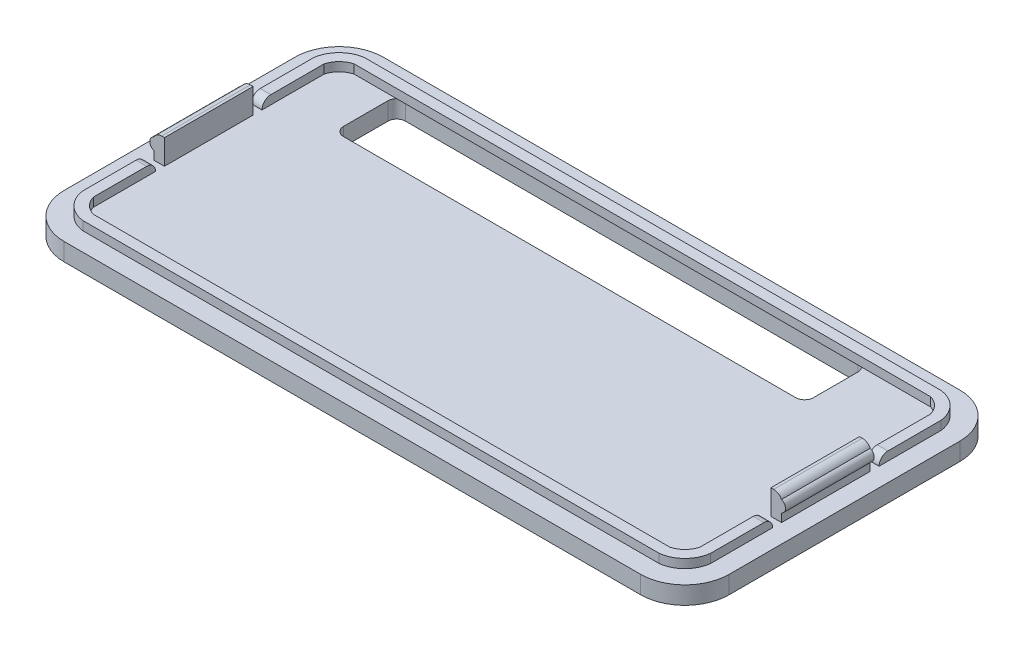
SolidWorks part; units mm, degrees
ref_plane "前视基准面" through (0, 0, 0) normal (0, 0, 1) x (1, 0, 0)
ref_plane "上视基准面" through (0, 0, 0) normal (0, 1, 0) x (1, 0, 0)
ref_plane "右视基准面" through (0, 0, 0) normal (1, 0, 0) x (0, 0, -1)
sketch "zero" plane through (0, 0, 0) normal (0, 1, 0) x (1, 0, 0)
  line L1 (-29.5, 15) -> (29.5, 15)
  line L2 (-32.5, 12) -> (-32.5, -12)
  line L3 (-29.5, -15) -> (29.5, -15)
  line L4 (32.5, 12) -> (32.5, -12)
  line L5 (-32.5, 15) -> (32.5, -15) construction
  line L6 (-32.5, -15) -> (32.5, 15) construction
  line L7 (-25.7, -15) -> (-14.5, -15)
  line L8 (-25.7, -15) -> (-25.7, -9.6569)
  line L9 (-25.7, -9.6569) -> (-14.5, -9.6569)
  line L10 (-14.5, -15) -> (-14.5, -9.6569)
  line L11 (5.2, -15) -> (12.7, -15)
  line L12 (5.2, -15) -> (5.2, -11)
  line L13 (5.2, -11) -> (12.7, -11)
  line L14 (12.7, -15) -> (12.7, -11)
  line L15 (17.8, -15) -> (25.3, -15)
  line L16 (17.8, -15) -> (17.8, -11)
  line L17 (17.8, -11) -> (25.3, -11)
  line L18 (25.3, -15) -> (25.3, -11)
  line L19 (-32.5, 7.7) -> (-19.5, 7.7)
  line L20 (-32.5, 7.7) -> (-32.5, -4.3)
  line L21 (-32.5, -4.3) -> (-19.5, -4.3)
  line L22 (-19.5, 7.7) -> (-19.5, -4.3)
  line L23 (-25.5, 14) -> (25.5, 14)
  line L24 (-25.5, 14) -> (-25.5, 8.8)
  line L25 (-25.5, 8.8) -> (25.5, 8.8)
  line L26 (25.5, 14) -> (25.5, 8.8)
  line L27 (-19.5, 7.2329) -> (-35.5, 7.2329)
  line L28 (-19.5, 7.2329) -> (-19.5, -3.7671)
  line L29 (-19.5, -3.7671) -> (-35.5, -3.7671)
  line L30 (-35.5, 7.2329) -> (-35.5, -3.7671)
  arc A0 (29.5, -15) -> (32.5, -12) centre (29.5, -12) ccw
  arc A1 (29.5, 15) -> (32.5, 12) centre (29.5, 12) cw
  arc A2 (-32.5, -12) -> (-29.5, -15) centre (-29.5, -12) ccw
  arc A3 (-29.5, 15) -> (-32.5, 12) centre (-29.5, 12) ccw
  circle A4 centre (-29, 11.4) radius 3
  circle A5 centre (-29, -11.5) radius 3
  circle A6 centre (29, 11.4) radius 3
  circle A7 centre (29, -11.5) radius 3
  circle A8 centre (-29, 11.4) radius 1.375
  circle A9 centre (-29, -11.5) radius 1.375
  circle A10 centre (29, -11.5) radius 1.375
  circle A11 centre (29, 11.4) radius 1.375
  point P0 (0, 0)
  dimension "D3" = 3
  dimension "D4" = 6
  dimension "D9" = 2.75
  dimension "D1" = 65
  dimension "D2" = 30
  dimension "D5" = 3.6
  dimension "D6" = 3.5
  dimension "D7" = 3.5
  dimension "D8" = 3.5
  dimension "D10" = 12
  dimension "D11" = 7.3
  dimension "D12" = 13
  dimension "D13" = 11.2
  dimension "D14" = 6.8
  dimension "D15" = 19.7
  dimension "D16" = 7.5
  dimension "D17" = 7.5
  dimension "D18" = 5.1
  dimension "D19" = 4
  dimension "D20" = 5.2
  dimension "D21" = 7
  dimension "D22" = 7
  dimension "D23" = 1
  dimension "D24" = 11
  dimension "D25" = 16
sketch "sugar" plane through (0, 0, 0) normal (0, 1, 0) x (1, 0, 0)
  line L1 (-29.5, 15) -> (29.5, 15)
  line L2 (-32.5, 12) -> (-32.5, -12)
  line L3 (-29.5, -15) -> (29.5, -15)
  line L4 (32.5, 12) -> (32.5, -12)
  line L5 (-32.5, 15) -> (32.5, -15) construction
  line L6 (-32.5, -15) -> (32.5, 15) construction
  line L7 (23.5, -11.5) -> (19.5, -11.5)
  line L8 (23.5, -11.5) -> (23.5, -13.9082)
  line L9 (23.5, -13.9082) -> (19.5, -13.9082)
  line L10 (19.5, -11.5) -> (19.5, -13.9082)
  line L11 (16, -11.0071) -> (8.5, -11.0071)
  line L12 (16, -11.0071) -> (16, -15)
  line L13 (16, -15) -> (8.5, -15)
  line L14 (8.5, -11.0071) -> (8.5, -15)
  line L15 (20.5, -13.9082) -> (22.5, -13.9082)
  line L16 (20.5, -13.9082) -> (20.5, -14.8173)
  line L17 (20.5, -14.8173) -> (22.5, -14.8173)
  line L18 (22.5, -13.9082) -> (22.5, -14.8173)
  arc A0 (29.5, 15) -> (32.5, 12) centre (29.5, 12) cw
  arc A1 (29.5, -15) -> (32.5, -12) centre (29.5, -12) ccw
  arc A2 (-32.5, -12) -> (-29.5, -15) centre (-29.5, -12) ccw
  arc A3 (-29.5, 15) -> (-32.5, 12) centre (-29.5, 12) ccw
  circle A4 centre (-29, 11.4) radius 3
  circle A5 centre (-29, 11.4) radius 1.375
  circle A6 centre (-29, -11.5) radius 3
  circle A7 centre (-29, -11.5) radius 1.375
  circle A8 centre (29, 11.4) radius 3
  circle A9 centre (29, 11.4) radius 1.375
  circle A10 centre (29, -11.5) radius 3
  circle A11 centre (29, -11.5) radius 1.375
  dimension "D3" = 3
  dimension "D1" = 65
  dimension "D2" = 30
  dimension "D4" = 9
  dimension "D5" = 4
  dimension "D6" = 3.5
  dimension "D7" = 7.5
  dimension "D8" = 2
  dimension "D9" = 1
sketch "case" plane through (0, 0, 0) normal (0, 1, 0) x (1, 0, 0)
  line L1 (-34.0422, 18) -> (30.9578, 18)
  line L2 (-39.0422, 13) -> (-39.0422, -13)
  line L3 (-34.0422, -18) -> (30.9578, -18)
  line L4 (35.9578, 13) -> (35.9578, -13)
  line L5 (-39.0422, 18) -> (35.9578, -18) construction
  line L6 (-39.0422, -18) -> (35.9578, 18) construction
  arc A0 (-39.0422, -13) -> (-34.0422, -18) centre (-34.0422, -13) ccw
  arc A1 (30.9578, -18) -> (35.9578, -13) centre (30.9578, -13) ccw
  arc A2 (30.9578, 18) -> (35.9578, 13) centre (30.9578, 13) cw
  arc A3 (-34.0422, 18) -> (-39.0422, 13) centre (-34.0422, 13) ccw
  point P0 (-1.5422, 0)
  point P3 (-1.5422, 0)
  dimension "D3" = 5
  dimension "D1" = 75
  dimension "D2" = 36
extrude "凸台-拉伸2" add sketch "case" along normal blind 2
sketch "草图2" plane through (0, 0, 0) normal (0, 1, 0) x (1, 0, 0)
  line L4 (-34.0422, -14.7) -> (30.9578, -14.7)
  line L5 (32.6578, -13) -> (32.6578, 13)
  line L6 (30.9578, 14.7) -> (-34.0422, 14.7)
  line L7 (-35.7422, 13) -> (-35.7422, -13)
  line L12 (33.8578, -13) -> (33.8578, 13)
  line L13 (30.9578, 15.9) -> (-34.0422, 15.9)
  line L14 (-36.9422, 13) -> (-36.9422, -13)
  line L15 (-34.0422, -15.9) -> (30.9578, -15.9)
  arc A4 (30.9578, -14.7) -> (32.6578, -13) centre (30.339, -12.3812) ccw
  arc A5 (32.6578, 13) -> (30.9578, 14.7) centre (30.339, 12.3812) ccw
  arc A6 (-34.0422, 14.7) -> (-35.7422, 13) centre (-33.4234, 12.3812) ccw
  arc A7 (-35.7422, -13) -> (-34.0422, -14.7) centre (-33.4234, -12.3812) ccw
  arc A12 (30.9578, -15.9) -> (33.8578, -13) centre (30.5796, -12.6217) ccw
  arc A13 (33.8578, 13) -> (30.9578, 15.9) centre (30.5796, 12.6217) ccw
  arc A14 (-34.0422, 15.9) -> (-36.9422, 13) centre (-33.6639, 12.6217) ccw
  arc A15 (-36.9422, -13) -> (-34.0422, -15.9) centre (-33.6639, -12.6217) ccw
  point P13 (0, 0)
  point P14 (0, 0)
ref_plane "基准面1" through (0, 2, 0) normal (0, 1, 0) x (1, 0, 0)
sketch "草图3" plane through (0, 2, 0) normal (0, 1, 0) x (1, 0, 0)
  line L4 (-34.0422, -14.7) -> (30.9578, -14.7)
  line L5 (32.6578, -13) -> (32.6578, 13)
  line L6 (30.9578, 14.7) -> (-34.0422, 14.7)
  line L7 (-35.7422, 13) -> (-35.7422, -13)
  line L8 (-34.0422, -14.7) -> (30.9578, -14.7)
  line L9 (32.6578, -13) -> (32.6578, 13)
  line L10 (30.9578, 14.7) -> (-34.0422, 14.7)
  line L11 (-35.7422, 13) -> (-35.7422, -13)
  line L12 (-36.9422, 13) -> (-36.9422, -13)
  line L13 (-34.0422, -15.9) -> (30.9578, -15.9)
  line L14 (33.8578, -13) -> (33.8578, 13)
  line L15 (30.9578, 15.9) -> (-34.0422, 15.9)
  line L16 (-36.9422, 13) -> (-36.9422, -13)
  line L17 (-34.0422, -15.9) -> (30.9578, -15.9)
  line L18 (33.8578, -13) -> (33.8578, 13)
  line L19 (30.9578, 15.9) -> (-34.0422, 15.9)
  arc A4 (30.9578, -14.7) -> (32.6578, -13) centre (30.339, -12.3812) ccw
  arc A5 (32.6578, 13) -> (30.9578, 14.7) centre (30.339, 12.3812) ccw
  arc A6 (-34.0422, 14.7) -> (-35.7422, 13) centre (-33.4234, 12.3812) ccw
  arc A7 (-35.7422, -13) -> (-34.0422, -14.7) centre (-33.4234, -12.3812) ccw
  arc A8 (30.9578, -14.7) -> (32.6578, -13) centre (30.339, -12.3812) ccw
  arc A9 (32.6578, 13) -> (30.9578, 14.7) centre (30.339, 12.3812) ccw
  arc A10 (-34.0422, 14.7) -> (-35.7422, 13) centre (-33.4234, 12.3812) ccw
  arc A11 (-35.7422, -13) -> (-34.0422, -14.7) centre (-33.4234, -12.3812) ccw
  arc A12 (-36.9422, -13) -> (-34.0422, -15.9) centre (-33.6639, -12.6217) ccw
  arc A13 (30.9578, -15.9) -> (33.8578, -13) centre (30.5796, -12.6217) ccw
  arc A14 (33.8578, 13) -> (30.9578, 15.9) centre (30.5796, 12.6217) ccw
  arc A15 (-34.0422, 15.9) -> (-36.9422, 13) centre (-33.6639, 12.6217) ccw
  arc A16 (-36.9422, -13) -> (-34.0422, -15.9) centre (-33.6639, -12.6217) ccw
  arc A17 (30.9578, -15.9) -> (33.8578, -13) centre (30.5796, -12.6217) ccw
  arc A18 (33.8578, 13) -> (30.9578, 15.9) centre (30.5796, 12.6217) ccw
  arc A19 (-34.0422, 15.9) -> (-36.9422, 13) centre (-33.6639, 12.6217) ccw
  dimension "D1" = 0
  dimension "D2" = 0
extrude "凸台-拉伸4" add sketch "草图3" along normal blind 1
ref_plane "基准面3" through (33.8578, 0, 0) normal (1, 0, 0) x (0, 0, -1)
sketch "草图7" plane through (0, 2, 0) normal (0, 1, 0) x (1, 0, 0)
  line L0 (-36.9422, 13) -> (-36.9422, -13) construction
  line L1 (-36.9422, 5) -> (-35.7422, 5)
  line L2 (-36.9422, 5) -> (-36.9422, -5)
  line L3 (-36.9422, -5) -> (-35.7422, -5)
  line L4 (-35.7422, 5) -> (-35.7422, -5)
  line L5 (-35.7422, 13) -> (-35.7422, -13) construction
  point P10 (-35.7422, 0)
  dimension "D1" = 5
  dimension "D2" = 10
extrude "凸台-拉伸8" add sketch "草图7" along normal blind 2.8
ref_plane "基准面5" through (0, 0, 5) normal (0, 0, 1) x (1, 0, 0)
sketch "草图8" plane through (0, 0, 5) normal (0, 0, 1) x (1, 0, 0)
  line L0 (-34.0422, 2) -> (-39.0422, 2) construction
  line L1 (-36.9422, 4.8) -> (-36.9422, 3) construction
  circle A0 centre (-36.6922, 3.6) radius 0.7
  dimension "D1" = 1.4
  dimension "D2" = 1.6
  dimension "D3" = 0.25
extrude "凸台-拉伸9" add sketch "草图8" against normal blind 10
fillet "圆角1" radius 1 1 edges at (-36.9422, 4.8, 0)
ref_plane "基准面7" through (-36.9422, 0, 0) normal (-1, 0, 0) x (0, 0, 1)
sketch "草图11" plane through (-36.9422, 0, 0) normal (-1, 0, 0) x (0, 0, 1)
  line L0 (-13, 2) -> (13, 2) construction
  line L1 (5, 3) -> (6, 3)
  line L2 (5, 3) -> (5, 2)
  line L3 (5, 2) -> (6, 2)
  line L4 (6, 3) -> (6, 2)
  line L6 (-5, 3) -> (-6, 3)
  line L7 (-5, 3) -> (-5, 2)
  line L8 (-5, 2) -> (-6, 2)
  line L9 (-6, 3) -> (-6, 2)
  dimension "D1" = 1
  dimension "D2" = 1
extrude "切除-拉伸1" cut sketch "草图11" against normal blind 1.2
fillet "圆角2" radius 1 2 edges at (-36.3422, 3, 6) (-36.3422, 3, -6)
ref_plane "基准面8" through (0, 0, 0) normal (0, -1, 0) x (-1, 0, 0)
sketch "草图12" plane through (0, 0, 0) normal (0, -1, 0) x (-1, 0, 0)
  line L76 (34.0422, -18) -> (-30.9578, -18) construction
  line L78 (39.0422, 13) -> (39.0422, -13) construction
  line B0 (-8.1993, 1.426) -> (-9.0198, 1.899)
  line B1 (-9.0198, 1.899) -> (-13.2767, 4.3551)
  line B2 (-13.2767, 4.3551) -> (-14.0973, 4.8339)
  line B3 (-15.8183, 4.8339) -> (-16.6389, 4.3551)
  line B4 (-16.6389, 4.3551) -> (-20.8958, 1.899)
  line B5 (-20.8958, 1.899) -> (-21.7165, 1.426)
  line B6 (-22.577, -0.0613) -> (-22.577, -6.8769)
  line B7 (-21.7165, -8.3643) -> (-20.8958, -8.8373)
  line B8 (-20.8958, -8.8373) -> (-16.6389, -11.2934)
  line B9 (-16.6389, -11.2934) -> (-15.8183, -11.772)
  line B10 (-14.0973, -11.772) -> (-13.2767, -11.2934)
  line B11 (-13.2767, -11.2934) -> (-9.0198, -8.8373)
  line B12 (-9.0198, -8.8373) -> (-8.1993, -8.3643)
  line B13 (-7.3388, -6.8769) -> (-7.3388, -0.0613)
  line B14 (-20.6223, 0.7479) -> (-15.3568, 3.791)
  line B15 (-14.5532, 3.791) -> (-9.3162, 0.7422)
  line B16 (-9.3105, 0.0413) -> (-14.3993, -3.0018)
  line B17 (-12.8208, -8.1591) -> (-13.4135, -8.4896)
  line B18 (-13.4705, -8.5865) -> (-13.4705, -10.2961)
  line B19 (-13.5274, -10.393) -> (-14.633, -11.0198)
  line B20 (-14.7983, -10.9229) -> (-14.7983, -5.646)
  line B21 (-14.7413, -5.5491) -> (-12.8607, -4.4835)
  line B22 (-8.9173, -7.8058) -> (-10.0114, -8.4269)
  line B23 (-10.1767, -8.3301) -> (-10.1767, -5.8169)
  line B24 (-10.1197, -5.7201) -> (-9.0256, -5.1046)
  line B25 (-8.8603, -5.2015) -> (-8.8603, -7.7089)
  line B26 (-12.8893, -7.1447) -> (-13.4135, -7.4069)
  line B27 (-13.4705, -7.2872) -> (-13.4705, -5.9423)
  line B28 (-13.4135, -5.8455) -> (-12.9234, -5.5719)
  line B29 (-3.344, -0.54) -> (-5.2189, -0.54)
  line B30 (-5.2189, -0.54) -> (-5.2189, -7.1048)
  line B31 (-5.2189, -7.1048) -> (-4.3868, -7.1048)
  line B32 (-4.3868, -7.1048) -> (-4.3868, -4.5005)
  line B33 (-4.3868, -4.5005) -> (-3.2984, -4.5005)
  line B34 (-3.4066, -3.8281) -> (-4.3868, -3.8281)
  line B35 (-4.3868, -3.8281) -> (-4.3868, -1.2124)
  line B36 (-4.3868, -1.2124) -> (-3.4408, -1.2124)
  line B37 (0.1948, -2.2382) -> (0.1948, -7.1048)
  line B38 (0.1948, -7.1048) -> (1.0098, -7.1048)
  line B39 (1.0098, -7.1048) -> (1.0098, -2.2382)
  line B40 (1.0098, -2.2382) -> (0.1948, -2.2382)
  line B41 (5.7169, -3.3153) -> (4.8849, -2.9847)
  line B42 (6.0417, -2.1983) -> (6.8396, -1.1953)
  line B43 (3.6084, -4.1586) -> (4.4575, -4.5177)
  line B44 (2.9074, -5.1673) -> (2.0014, -6.2729)
  line B45 (10.8229, -2.0102) -> (10.8229, -5.3497)
  line B46 (9.3811, -4.9621) -> (9.3811, -2.0102)
  line B47 (9.3811, -2.0102) -> (7.7912, -2.0102)
  line B48 (7.7912, -2.0102) -> (7.7912, -5.1616)
  line B49 (10.9711, -6.4039) -> (11.0052, -6.4039)
  line B50 (11.0052, -6.4039) -> (11.1193, -7.1048)
  line B51 (11.1193, -7.1048) -> (12.4185, -7.1048)
  line B52 (12.4185, -7.1048) -> (12.4185, -2.0102)
  line B53 (12.4185, -2.0102) -> (10.8229, -2.0102)
  line B54 (16.2708, -6.1019) -> (15.4673, -6.1019)
  line B55 (17.365, -3.1614) -> (18.1513, -3.1614)
  line B56 (18.1513, -3.1614) -> (18.1513, -2.0102)
  line B57 (18.1513, -2.0102) -> (16.2822, -2.0102)
  line B58 (14.0312, -5.0533) -> (14.0312, -5.0875)
  line B59 (13.9344, -6.9168) -> (13.9344, -6.9624)
  line B60 (15.4844, -7.3214) -> (15.9688, -7.3214)
  line B61 (18.6072, -2.5516) -> (19.1657, -3.6002)
  line B62 (21.411, -6.592) -> (21.4508, -6.592)
  line B63 (21.4508, -6.592) -> (21.5648, -7.1048)
  line B64 (21.5648, -7.1048) -> (22.8641, -7.1048)
  line B65 (22.8641, -7.1048) -> (22.8641, -4.2099)
  line B66 (21.2685, -4.7741) -> (21.2685, -5.589)
  line B67 (25.3545, -2.8935) -> (25.3203, -2.8935)
  line B68 (25.3203, -2.8935) -> (25.212, -2.0102)
  line B69 (25.212, -2.0102) -> (23.9127, -2.0102)
  line B70 (23.9127, -2.0102) -> (23.9127, -7.1048)
  line B71 (23.9127, -7.1048) -> (25.4969, -7.1048)
  line B72 (25.4969, -7.1048) -> (25.4969, -4.1928)
  line B73 (27.1552, -3.3608) -> (27.423, -1.9875)
  line B74 (-13.4135, -7.4069) -> (-13.4135, -8.4896)
  line B75 (-13.4705, -7.2872) -> (-13.4705, -8.5865)
  spline B76 degree 3 poles (-14.0973, 4.8339) (-14.3652, 4.982) (-14.6615, 5.0618) (-14.9578, 5.0618) knots 3 3 3 3 4 4 4 4
  spline B77 degree 3 poles (-14.9578, 5.0618) (-15.2541, 5.0618) (-15.5505, 4.982) (-15.8183, 4.8339) knots 4 4 4 4 5 5 5 5
  spline B78 degree 3 poles (-21.7165, 1.426) (-22.2464, 1.1183) (-22.577, 0.5485) (-22.577, -0.0613) knots 8 8 8 8 9 9 9 9
  spline B79 degree 3 poles (-22.577, -6.8769) (-22.577, -7.4923) (-22.2464, -8.0565) (-21.7165, -8.3643) knots 10 10 10 10 11 11 11 11
  spline B80 degree 3 poles (-15.8183, -11.772) (-15.5505, -11.9259) (-15.2541, -12) (-14.9578, -12) knots 14 14 14 14 15 15 15 15
  spline B81 degree 3 poles (-14.9578, -12) (-14.6615, -12) (-14.3652, -11.9259) (-14.0973, -11.772) knots 15 15 15 15 16 16 16 16
  spline B82 degree 3 poles (-8.1993, -8.3643) (-7.6636, -8.0565) (-7.3388, -7.4923) (-7.3388, -6.8769) knots 19 19 19 19 20 20 20 20
  spline B83 degree 3 poles (-7.3388, -0.0613) (-7.3388, 0.5485) (-7.6636, 1.1183) (-8.1993, 1.426) knots 21 21 21 21 22 22 22 22
  spline B84 degree 2 poles (-15.5106, -3.0018) (-20.6622, -0.0271) (-20.6736, -0.0214) knots 0 0 0 1 1 1
  spline B85 degree 3 poles (-20.6736, -0.0214) (-20.9414, 0.1723) (-20.9129, 0.5826) (-20.6223, 0.7479) knots 1 1 1 1 2 2 2 2
  spline B86 degree 3 poles (-15.3568, 3.791) (-15.1117, 3.9335) (-14.8039, 3.9335) (-14.5532, 3.791) knots 3 3 3 3 4 4 4 4
  spline B87 degree 3 poles (-9.3162, 0.7422) (-9.0484, 0.5883) (-9.0427, 0.2008) (-9.3105, 0.0413) knots 5 5 5 5 6 6 6 6
  spline B88 degree 3 poles (-14.3993, -3.0018) (-14.7413, -3.2013) (-15.1687, -3.2013) (-15.5106, -3.0018) knots 7 7 7 7 8 8 8 8
  spline B89 degree 3 poles (-13.4705, -10.2961) (-13.4705, -10.336) (-13.4876, -10.3702) (-13.5274, -10.393) knots 3 3 3 3 4 4 4 4
  spline B90 degree 3 poles (-14.633, -11.0198) (-14.7071, -11.0597) (-14.7983, -11.0084) (-14.7983, -10.9229) knots 5 5 5 5 6 6 6 6
  spline B91 degree 3 poles (-14.7983, -5.646) (-14.7983, -5.6061) (-14.7812, -5.5662) (-14.7413, -5.5491) knots 7 7 7 7 8 8 8 8
  spline B92 degree 3 poles (-12.8607, -4.4835) (-11.6412, -3.7939) (-10.6326, -3.6572) (-10.6326, -5.0249) knots 9 9 9 9 10 10 10 10
  spline B93 degree 3 poles (-10.6326, -5.0249) (-10.6326, -6.3412) (-11.6526, -7.498) (-12.8208, -8.1591) knots 10 10 10 10 11 11 11 11
  spline B94 degree 3 poles (-8.8603, -7.7089) (-8.8603, -7.7488) (-8.8831, -7.7887) (-8.9173, -7.8058) knots 0 0 0 0 1 1 1 1
  spline B95 degree 3 poles (-10.0114, -8.4269) (-10.0855, -8.4668) (-10.1767, -8.4155) (-10.1767, -8.3301) knots 2 2 2 2 3 3 3 3
  spline B96 degree 3 poles (-10.1767, -5.8169) (-10.1767, -5.7771) (-10.1539, -5.7429) (-10.1197, -5.7201) knots 4 4 4 4 5 5 5 5
  spline B97 degree 3 poles (-9.0256, -5.1046) (-8.9515, -5.0647) (-8.8603, -5.116) (-8.8603, -5.2015) knots 6 6 6 6 7 7 7 7
  spline B98 degree 3 poles (-9.5156, -3.4349) (-9.0768, -3.1842) (-8.7634, -3.2924) (-8.7634, -3.6914) (-8.7634, -4.0846) (-9.0768, -4.5461) (-9.5156, -4.7912) knots 2 2 2 2 3 3 3 4 4 4 4
  spline B99 degree 3 poles (-9.5156, -4.7912) (-9.9601, -5.0476) (-10.2735, -4.9394) (-10.2735, -4.5461) (-10.2735, -4.1415) (-9.9601, -3.6856) (-9.5156, -3.4349) knots 0 0 0 0 1 1 1 2 2 2 2
  spline B100 degree 3 poles (-11.9319, -5.76) (-11.9319, -6.3013) (-12.2395, -6.78) (-12.8893, -7.1447) knots 0 0 0 0 1 1 1 1
  spline B101 degree 3 poles (-13.4705, -5.9423) (-13.4705, -5.9024) (-13.4477, -5.8625) (-13.4135, -5.8455) knots 4 4 4 4 5 5 5 5
  spline B102 degree 3 poles (-12.9234, -5.5719) (-12.2852, -5.2072) (-11.9319, -5.2015) (-11.9319, -5.76) knots 6 6 6 6 7 7 7 7
  spline B103 degree 3 poles (-3.2984, -4.5005) (-1.868, -4.5005) (-0.8822, -3.8509) (-0.8822, -2.4661) knots 5 5 5 5 6 6 6 6
  spline B104 degree 3 poles (-0.8822, -2.4661) (-0.8822, -1.0301) (-1.868, -0.54) (-3.344, -0.54) knots 6 6 6 6 7 7 7 7
  spline B105 degree 3 poles (-3.4408, -1.2124) (-2.2897, -1.2124) (-1.7084, -1.5145) (-1.7084, -2.4661) knots 3 3 3 3 4 4 4 4
  spline B106 degree 3 poles (-1.7084, -2.4661) (-1.7084, -3.4064) (-2.2498, -3.8281) (-3.4066, -3.8281) knots 4 4 4 4 5 5 5 5
  spline B107 degree 3 poles (0.6052, -1.2352) (0.93, -1.2352) (1.1694, -1.013) (1.1694, -0.711) (1.1694, -0.3747) (0.93, -0.181) (0.6052, -0.181) knots 2 2 2 2 3 3 3 4 4 4 4
  spline B108 degree 3 poles (0.6052, -0.181) (0.2804, -0.181) (0.041, -0.3747) (0.041, -0.711) (0.041, -1.013) (0.2804, -1.2352) (0.6052, -1.2352) knots 0 0 0 0 1 1 1 2 2 2 2
  spline B109 degree 3 poles (4.8849, -2.9847) (4.2979, -2.7511) (3.8762, -2.6086) (3.8762, -2.2382) knots 1 1 1 1 2 2 2 2
  spline B110 degree 3 poles (3.8762, -2.2382) (3.8762, -1.8849) (4.1783, -1.6854) (4.674, -1.6854) knots 2 2 2 2 3 3 3 3
  spline B111 degree 3 poles (4.674, -1.6854) (5.1926, -1.6854) (5.6029, -1.8621) (6.0417, -2.1983) knots 3 3 3 3 4 4 4 4
  spline B112 degree 3 poles (6.8396, -1.1953) (6.2583, -0.6084) (5.4433, -0.3121) (4.674, -0.3121) knots 5 5 5 5 6 6 6 6
  spline B113 degree 3 poles (4.674, -0.3121) (3.2551, -0.3121) (2.2521, -1.2124) (2.2521, -2.3294) knots 6 6 6 6 7 7 7 7
  spline B114 degree 3 poles (2.2521, -2.3294) (2.2521, -3.2981) (2.9074, -3.8794) (3.6084, -4.1586) knots 7 7 7 7 8 8 8 8
  spline B115 degree 3 poles (4.4575, -4.5177) (5.0274, -4.757) (5.3978, -4.8824) (5.3978, -5.2699) knots 9 9 9 9 10 10 10 10
  spline B116 degree 3 poles (5.3978, -5.2699) (5.3978, -5.6289) (5.1185, -5.8511) (4.5259, -5.8511) knots 10 10 10 10 11 11 11 11
  spline B117 degree 3 poles (4.5259, -5.8511) (4.0016, -5.8511) (3.3804, -5.5719) (2.9074, -5.1673) knots 11 11 11 11 12 12 12 12
  spline B118 degree 3 poles (2.0014, -6.2729) (2.6909, -6.9054) (3.6254, -7.2302) (4.4916, -7.2302) knots 13 13 13 13 14 14 14 14
  spline B119 degree 3 poles (4.4916, -7.2302) (6.1044, -7.2302) (7.0389, -6.2557) (7.0389, -5.1445) knots 14 14 14 14 15 15 15 15
  spline B120 degree 3 poles (7.0389, -5.1445) (7.0389, -4.2042) (6.5432, -3.6458) (5.7169, -3.3153) knots 15 15 15 15 16 16 16 16
  spline B121 degree 3 poles (10.8229, -5.3497) (10.5551, -5.7258) (10.3328, -5.8682) (9.9738, -5.8682) knots 1 1 1 1 2 2 2 2
  spline B122 degree 3 poles (9.9738, -5.8682) (9.5692, -5.8682) (9.3811, -5.6688) (9.3811, -4.9621) knots 2 2 2 2 3 3 3 3
  spline B123 degree 3 poles (7.7912, -5.1616) (7.7912, -6.4324) (8.2642, -7.2302) (9.3754, -7.2302) knots 6 6 6 6 7 7 7 7
  spline B124 degree 3 poles (9.3754, -7.2302) (10.0706, -7.2302) (10.5494, -6.9054) (10.9711, -6.4039) knots 7 7 7 7 8 8 8 8
  spline B125 degree 3 poles (15.4673, -6.1019) (14.9202, -6.1019) (14.7151, -5.9936) (14.7151, -5.76) knots 1 1 1 1 2 2 2 2
  spline B126 degree 3 poles (14.7151, -5.76) (14.7151, -5.589) (14.7549, -5.5092) (14.8746, -5.4009) knots 2 2 2 2 3 3 3 3
  spline B127 degree 3 poles (14.8746, -5.4009) (15.0969, -5.4636) (15.302, -5.4921) (15.473, -5.4921) knots 3 3 3 3 4 4 4 4
  spline B128 degree 3 poles (15.473, -5.4921) (16.6013, -5.4921) (17.5074, -4.9735) (17.5074, -3.7825) knots 4 4 4 4 5 5 5 5
  spline B129 degree 3 poles (17.5074, -3.7825) (17.5074, -3.5375) (17.4447, -3.3038) (17.365, -3.1614) knots 5 5 5 5 6 6 6 6
  spline B130 degree 3 poles (16.2822, -2.0102) (16.0485, -1.9248) (15.7693, -1.8849) (15.473, -1.8849) knots 9 9 9 9 10 10 10 10
  spline B131 degree 3 poles (15.473, -1.8849) (14.3732, -1.8849) (13.3417, -2.4889) (13.3417, -3.7369) knots 10 10 10 10 11 11 11 11
  spline B132 degree 3 poles (13.3417, -3.7369) (13.3417, -4.3296) (13.6722, -4.8026) (14.0312, -5.0533) knots 11 11 11 11 12 12 12 12
  spline B133 degree 3 poles (14.0312, -5.0875) (13.7007, -5.3212) (13.467, -5.6802) (13.467, -6.0392) knots 13 13 13 13 14 14 14 14
  spline B134 degree 3 poles (13.467, -6.0392) (13.467, -6.4666) (13.6665, -6.7344) (13.9344, -6.9168) knots 14 14 14 14 15 15 15 15
  spline B135 degree 3 poles (13.9344, -6.9624) (13.4613, -7.2017) (13.2106, -7.5436) (13.2106, -7.9653) knots 16 16 16 16 17 17 17 17
  spline B136 degree 3 poles (13.2106, -7.9653) (13.2106, -8.8771) (14.1737, -9.2475) (15.3476, -9.2475) knots 17 17 17 17 18 18 18 18
  spline B137 degree 3 poles (15.3476, -9.2475) (17.1199, -9.2475) (18.2312, -8.4839) (18.2312, -7.4069) knots 18 18 18 18 19 19 19 19
  spline B138 degree 3 poles (18.2312, -7.4069) (18.2312, -6.4837) (17.5245, -6.1019) (16.2708, -6.1019) knots 19 19 19 19 20 20 20 20
  spline B139 degree 3 poles (15.473, -4.5347) (15.1083, -4.5347) (14.8291, -4.2669) (14.8291, -3.7369) (14.8291, -3.2184) (15.1083, -2.9505) (15.473, -2.9505) knots 2 2 2 2 3 3 3 4 4 4 4
  spline B140 degree 3 poles (15.473, -2.9505) (15.8491, -2.9505) (16.1169, -3.2184) (16.1169, -3.7369) (16.1169, -4.2669) (15.8491, -4.5347) (15.473, -4.5347) knots 0 0 0 0 1 1 1 2 2 2 2
  spline B141 degree 3 poles (15.5983, -8.2503) (14.943, -8.2503) (14.5156, -8.0736) (14.5156, -7.7146) knots 0 0 0 0 1 1 1 1
  spline B142 degree 3 poles (14.5156, -7.7146) (14.5156, -7.5436) (14.5953, -7.4012) (14.7549, -7.2587) knots 1 1 1 1 2 2 2 2
  spline B143 degree 3 poles (14.7549, -7.2587) (14.9202, -7.3043) (15.114, -7.3214) (15.4844, -7.3214) knots 2 2 2 2 3 3 3 3
  spline B144 degree 3 poles (15.9688, -7.3214) (16.4417, -7.3214) (16.7096, -7.3841) (16.7096, -7.6861) knots 4 4 4 4 5 5 5 5
  spline B145 degree 3 poles (16.7096, -7.6861) (16.7096, -8.0109) (16.2537, -8.2503) (15.5983, -8.2503) knots 5 5 5 5 6 6 6 6
  spline B146 degree 3 poles (20.8013, -1.8849) (20.0091, -1.8849) (19.2797, -2.1527) (18.6072, -2.5516) knots 0 0 0 0 1 1 1 1
  spline B147 degree 3 poles (19.1657, -3.6002) (19.6729, -3.3153) (20.0946, -3.1557) (20.4992, -3.1557) knots 2 2 2 2 3 3 3 3
  spline B148 degree 3 poles (20.4992, -3.1557) (21.0177, -3.1557) (21.2344, -3.395) (21.2685, -3.8053) knots 3 3 3 3 4 4 4 4
  spline B149 degree 3 poles (21.2685, -3.8053) (19.2797, -4.0219) (18.4362, -4.6031) (18.4362, -5.6802) knots 4 4 4 4 5 5 5 5
  spline B150 degree 3 poles (18.4362, -5.6802) (18.4362, -6.5293) (19.0118, -7.2302) (19.9522, -7.2302) knots 5 5 5 5 6 6 6 6
  spline B151 degree 3 poles (19.9522, -7.2302) (20.5163, -7.2302) (20.9893, -6.9681) (21.411, -6.592) knots 6 6 6 6 7 7 7 7
  spline B152 degree 3 poles (22.8641, -4.2099) (22.8641, -2.6143) (22.1176, -1.8849) (20.8013, -1.8849) knots 11 11 11 11 12 12 12 12
  spline B153 degree 3 poles (21.2685, -5.589) (21.0349, -5.8398) (20.824, -5.9936) (20.4992, -5.9936) knots 0 0 0 0 1 1 1 1
  spline B154 degree 3 poles (20.4992, -5.9936) (20.1686, -5.9936) (19.9522, -5.8511) (19.9522, -5.5548) knots 1 1 1 1 2 2 2 2
  spline B155 degree 3 poles (19.9522, -5.5548) (19.9522, -5.1958) (20.277, -4.9109) (21.2685, -4.7741) knots 2 2 2 2 3 3 3 3
  spline B156 degree 3 poles (26.8076, -1.8849) (26.2947, -1.8849) (25.7305, -2.2154) (25.3545, -2.8935) knots 0 0 0 0 1 1 1 1
  spline B157 degree 3 poles (25.4969, -4.1928) (25.7648, -3.5204) (26.2207, -3.2811) (26.5967, -3.2811) knots 7 7 7 7 8 8 8 8
  spline B158 degree 3 poles (26.5967, -3.2811) (26.8247, -3.2811) (26.9729, -3.3153) (27.1552, -3.3608) knots 8 8 8 8 9 9 9 9
  spline B159 degree 3 poles (27.423, -1.9875) (27.2806, -1.9248) (27.1096, -1.8849) (26.8076, -1.8849) knots 10 10 10 10 11 11 11 11
  dimension "D1" = 6
  dimension "D2" = 54
sketch_block_instance "块1-1"
sketch_block "块1"
extrude "切除-拉伸2" cut sketch "草图12" against normal blind 0.5
sketch "草图13" plane through (0, 0, 0) normal (0, 1, 0) x (1, 0, 0)
  line L0 (30.9578, 18) -> (-34.0422, 18) construction
  line L1 (-29.5422, 15) -> (23.4578, 15)
  line L2 (-29.5422, 15) -> (-29.5422, 8)
  line L3 (-29.5422, 8) -> (23.4578, 8)
  line L4 (23.4578, 15) -> (23.4578, 8)
  line L6 (-39.0422, 13) -> (-39.0422, -13) construction
  dimension "D1" = 7
  dimension "D2" = 53
  dimension "D3" = 3
  dimension "D4" = 9.5
extrude "切除-拉伸3" cut sketch "草图13" along normal blind 2
fillet "圆角3" radius 1 4 edges at (-29.5422, 1, -15) (-29.5422, 1, -8) (23.4578, 1, -15) (23.4578, 1, -8)
sketch "草图14" plane through (0, 3, 0) normal (0, 1, 0) x (1, 0, 0)
  line L0 (33.8578, -13) -> (33.8578, 13) construction
  line L1 (33.8578, 5) -> (32.6578, 5)
  line L2 (33.8578, 5) -> (33.8578, -5)
  line L3 (33.8578, -5) -> (32.6578, -5)
  line L4 (32.6578, 5) -> (32.6578, -5)
  line L5 (32.6578, -13) -> (32.6578, 13) construction
  line L6 (35.9578, -13) -> (35.9578, 13) construction
  point P10 (33.8578, 0)
  point P11 (35.9578, 0)
  dimension "D1" = 10
extrude "凸台-拉伸10" add sketch "草图14" along normal blind 1.8
sketch "草图15" plane through (0, 0, -5) normal (0, 0, -1) x (-1, 0, 0)
  line L0 (-30.9578, 2) -> (-35.9578, 2) construction
  line L1 (-33.8578, 4.8) -> (-33.8578, 3) construction
  circle A0 centre (-33.6078, 3.6) radius 0.7
  dimension "D1" = 1.4
  dimension "D2" = 1.6
  dimension "D3" = 0.25
extrude "凸台-拉伸11" add sketch "草图15" against normal blind 10 contours A0
fillet "圆角4" radius 1 1 edges at (33.8578, 4.8, 0)
sketch "草图16" plane through (0, 3, 0) normal (0, 1, 0) x (1, 0, 0)
  line L0 (33.8578, -13) -> (33.8578, -5) construction
  line L1 (32.6578, -5) -> (33.8578, -5)
  line L2 (32.6578, -5) -> (32.6578, -6)
  line L3 (32.6578, -6) -> (33.8578, -6)
  line L4 (33.8578, -5) -> (33.8578, -6)
  line L5 (33.8578, 5) -> (33.8578, 13) construction
  line L6 (32.6578, 5) -> (33.8578, 5)
  line L7 (32.6578, 5) -> (32.6578, 6)
  line L8 (32.6578, 6) -> (33.8578, 6)
  line L9 (33.8578, 5) -> (33.8578, 6)
  dimension "D1" = 1
  dimension "D2" = 1
extrude "切除-拉伸4" cut sketch "草图16" against normal blind 1
fillet "圆角5" radius 1 2 edges at (33.2578, 3, 6) (33.2578, 3, -6)
